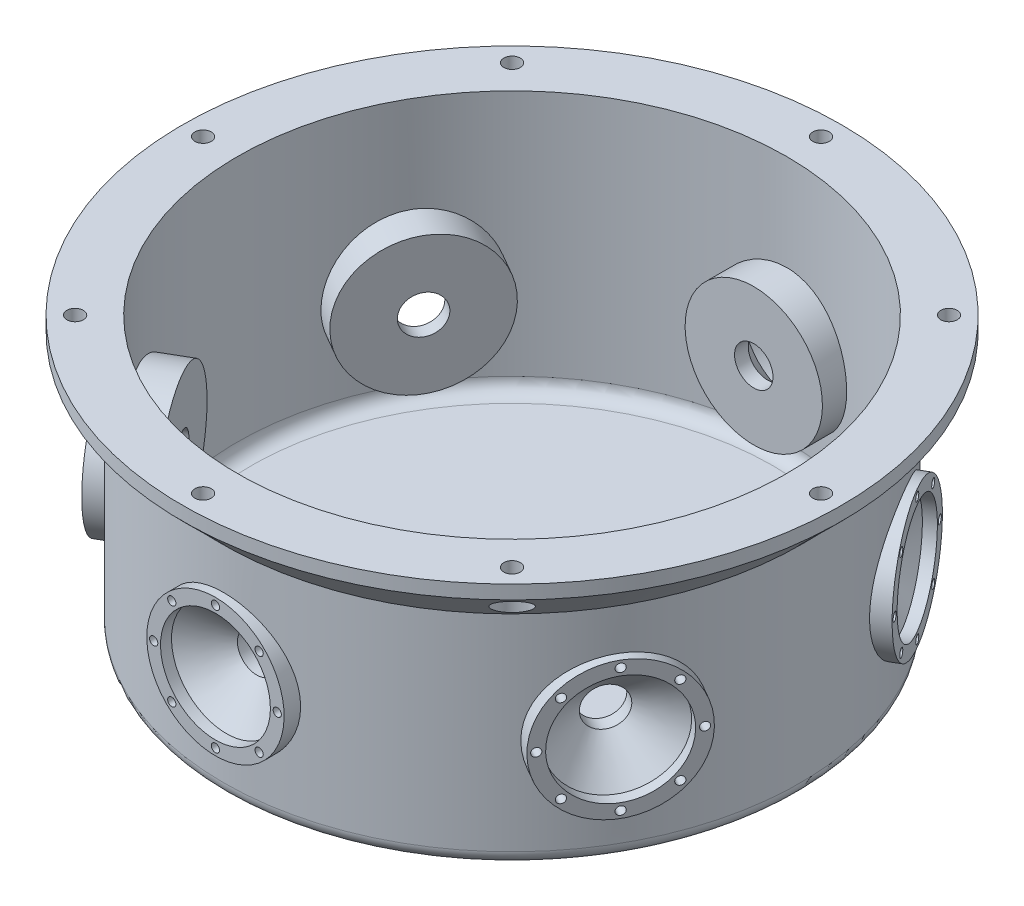
SolidWorks part; units mm, degrees
material "6061-T6 (SS)"
ref_plane "Front Plane" through (0, 0, 0) normal (0, 0, 1) x (1, 0, 0)
ref_plane "Top Plane" through (0, 0, 0) normal (0, 1, 0) x (1, 0, 0)
ref_plane "Right Plane" through (0, 0, 0) normal (1, 0, 0) x (0, 0, -1)
sketch "Sketch1" plane through (0, 0, 0) normal (0, 0, 1) x (1, 0, 0)
  line L0 (0, 0) -> (0, 96.1303) construction
  line L1 (0, 0) -> (-105, 0)
  line L2 (-105, 0) -> (-105, 80)
  line L3 (-105, 80) -> (-120, 95)
  line L4 (-120, 95) -> (-120, 100)
  line L5 (-120, 100) -> (-100, 100)
  line L6 (-100, 100) -> (-100, 5)
  line L7 (-100, 5) -> (0, 5)
  line L8 (0, 5) -> (0, 0)
  dimension "D1" = 200
  dimension "D2" = 5
  dimension "D3" = 5
  dimension "D4" = 5
  dimension "D5" = 20
  dimension "D6" = 45
  dimension "D7" = 100
revolve "Revolve1" add sketch "Sketch1" angle 360 about L0
sketch "Sketch2" plane through (0, 100, 0) normal (0, 1, 0) x (1, 0, 0)
  circle A0 centre (0, 0) radius 112.5 construction
  circle A1 centre (0, 112.5) radius 3
  circle A2 centre (0, 112.5) radius 6
  dimension "D1" = 225
  dimension "D2" = 6
  dimension "D3" = 12
extrude "Cut-Extrude1" cut sketch "Sketch2" against normal through all contours A1 region at (0, 100, -112.5)
extrude "Cut-Extrude2" cut sketch "Sketch2<3>" against normal through all from offset 5 offset against normal yes
sketch "Sketch2<3>" plane through (0, 100, 0) normal (0, 1, 0) x (1, 0, 0) same geometry as "Sketch2"
pattern_circular "CirPattern1" count 8 over 360 about axis through (0, 100, 0) along (0, -1, 0) of "Cut-Extrude1", "Cut-Extrude2"
sketch "Sketch3" plane through (0, 0, 0) normal (0, 0, 1) x (1, 0, 0)
  line L0 (0, 0) -> (0, 80) construction
  line L1 (105, 80) -> (-105, 80) construction
  circle A0 centre (0, 40) radius 25
  point P8 (0, 40)
  dimension "D1" = 50
extrude "Cut-Extrude3" cut sketch "Sketch3" along normal through all
sketch "Sketch7" plane through (0, 0, 0) normal (1, 0, 0) x (0, 0, -1)
  line L0 (17.469, 40) -> (-121.4429, 40) construction
  line L1 (0, 80) -> (0, 0) construction
  line L2 (105, 80) -> (-105, 80) construction
  line L4 (-108, 60) -> (-104, 60)
  line L5 (-104, 60) -> (-93, 47)
  line L6 (-93, 47) -> (-88, 47)
  line L7 (-88, 47) -> (-88, 65)
  line L8 (-88, 65) -> (-108, 65)
  line L9 (-108, 65) -> (-108, 60)
  point P7 (0, 40)
  dimension "D1" = 14
  dimension "D2" = 15
  dimension "D3" = 40
  dimension "D4" = 5
  dimension "D5" = 5
  dimension "D6" = 4
  dimension "D7" = 108
revolve "Revolve2" add sketch "Sketch7" angle 360 about L0
sketch "Sketch10" plane through (0, 0, 108) normal (0, 0, 1) x (1, 0, 0)
  circle A0 centre (0, 40) radius 22.5 construction
  circle A1 centre (0, 62.5) radius 1.5
  circle A2 centre (15.9099, 55.9099) radius 1.5
  circle A3 centre (22.5, 40) radius 1.5
  circle A4 centre (15.9099, 24.0901) radius 1.5
  circle A5 centre (0, 17.5) radius 1.5
  circle A6 centre (-15.9099, 24.0901) radius 1.5
  circle A7 centre (-22.5, 40) radius 1.5
  circle A8 centre (-15.9099, 55.9099) radius 1.5
  point P21 (0, 40)
  dimension "D1" = 45
  dimension "D2" = 3
  dimension "D3" = 8
extrude "Cut-Extrude6" cut sketch "Sketch10" against normal blind 4
pattern_circular "CirPattern2" count 6 over 360 about axis through (0, 100, 0) along (0, -1, 0) of "Cut-Extrude3", "Revolve2", "Cut-Extrude6"
fillet "Fillet2" radius 5 2 edges at (0, 5, -100) (0, 0, -105)
sketch "Sketch12" plane through (0, 0, 0) normal (0, -1, 0) x (1, 0, 0)
  circle A0 centre (0, 0) radius 8
  circle A1 centre (0, 0) radius 16
  dimension "D1" = 16
  dimension "D2" = 32
extrude "Boss-Extrude2" add sketch "Sketch12" along normal blind 25
cosmetic thread "Cosmetic Thread1" parameters "D2"=18
fillet "Fillet5" radius 5 1 edges at (0, 0, 16)
